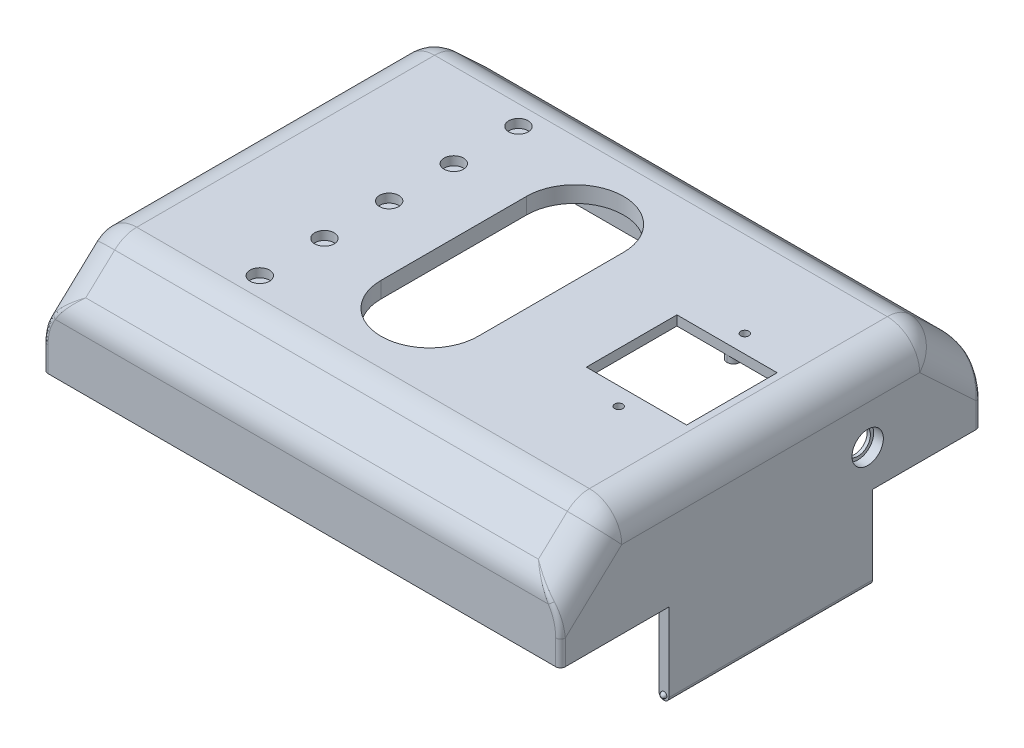
SolidWorks part; units mm, degrees
ref_plane "Front Plane" through (0, 0, 0) normal (0, 0, 1) x (1, 0, 0)
ref_plane "Top Plane" through (0, 0, 0) normal (0, 1, 0) x (1, 0, 0)
ref_plane "Right Plane" through (0, 0, 0) normal (1, 0, 0) x (0, 0, -1)
sketch "Sketch2" plane through (0, 0, 0) normal (0, 1, 0) x (1, 0, 0)
  line L0 (-80, 65) -> (80, -65) construction
  line L1 (-80, -65) -> (80, -65)
  line L2 (-80, -65) -> (-80, 65)
  line L3 (-80, 65) -> (80, 65)
  line L4 (80, -65) -> (80, 65)
  line L5 (-80, -65) -> (80, 65) construction
  point P4 (0, 0)
  dimension "D1" = 160
  dimension "D2" = 130
extrude "Boss-Extrude1" add sketch "Sketch2" along normal blind 5
sketch "Sketch3" plane through (-80, 0, 0) normal (-1, 0, 0) x (0, 0, 1)
  line L0 (-60, 4.8954) -> (60, 4.8954)
  line L1 (65, 5) -> (65, 0) construction
  line L2 (-65, 5) -> (65, 5) construction
  line L3 (-65, 5) -> (-65, 0) construction
  line L4 (65, 5) -> (65, 0)
  line L5 (-65, 5) -> (65, 5)
  line L6 (-65, 5) -> (-65, 0)
  arc A0 (-60, 4.8954) -> (-65, 0) centre (-60, -0.1057) ccw
  arc A1 (60, 4.8954) -> (65, 0) centre (60, -0.1057) cw
  point P2 (0, 4.8954)
  dimension "D1" = 120
  dimension "D2" = 5.0011
extrude "Cut-Extrude1" [suppressed] cut sketch "Sketch3" against normal through all
sketch "Sketch4" plane through (0, 0, 0) normal (0, -1, 0) x (1, 0, 0)
  line L0 (80, 65) -> (80, -65) construction
  line L1 (80, 31.5) -> (77, 31.5)
  line L2 (80, 31.5) -> (80, -31.5)
  line L3 (80, -31.5) -> (77, -31.5)
  line L4 (77, 31.5) -> (77, -31.5)
  point P6 (77, 0)
  dimension "D1" = 3
  dimension "D2" = 63
extrude "Boss-Extrude2" add sketch "Sketch4" along normal blind 25.75
sketch "Sketch15" plane through (-80, 0, 0) normal (-1, 0, 0) x (0, 0, 1)
  line L0 (-65, 0) -> (-65, 20)
  line L1 (-65, 20) -> (-50, 34)
  line L2 (-50, 34) -> (50, 34)
  line L3 (50, 34) -> (65, 20)
  line L4 (65, 20) -> (65, 0)
  line L5 (65, 0) -> (-65, 0)
  dimension "D1" = 34
  dimension "D2" = 20
  dimension "D3" = 100
extrude "Boss-Extrude5" add sketch "Sketch15" against normal blind 160
sketch "Sketch16" plane through (0, 0, 0) normal (0, -1, 0) x (1, 0, 0)
  line L1 (-76, 62) -> (76, 62)
  line L5 (-76, 62) -> (76, -62) construction
  line L6 (-76, -62) -> (76, 62) construction
  line L7 (-80, 65) -> (80, 65) construction
  line L8 (76, 62) -> (76, -62)
  line L9 (76, -62) -> (-63, -62)
  line L14 (-76, 62) -> (-76, -51.25)
  line L15 (-76, -51.25) -> (-62.8226, -51.25)
  line L16 (-62.8226, -51.25) -> (-63, -62)
  line L17 (-80, -65) -> (-80, 65) construction
  point P0 (0, 0)
  dimension "D1" = 139
  dimension "D2" = 3
  dimension "D3" = 113.25
  dimension "D4" = 4
extrude "Cut-Extrude9" cut sketch "Sketch16" against normal blind 20
sketch "Sketch17" plane through (0, 20, 0) normal (0, -1, 0) x (1, 0, 0)
  line L1 (-76, 50) -> (76, 50)
  line L2 (-76, 50) -> (-76, -50)
  line L3 (-76, -50) -> (76, -50)
  line L4 (76, 50) -> (76, -50)
  line L5 (-76, 50) -> (76, -50) construction
  line L6 (-76, -50) -> (76, 50) construction
  line L7 (80, -65) -> (-80, -65) construction
  line L8 (-80, -65) -> (-80, 65) construction
  point P0 (0, 0)
  dimension "D1" = 15
  dimension "D2" = 4
extrude "Cut-Extrude10" cut sketch "Sketch17" against normal offset from surface (9 mm away) 5 up to face at (0, 34, 0)
fillet "Fillet3" radius 10 10 edges at (-80, 27, 57.5) (-80, 34, 0) (-80, 27, -57.5) (80, 34, 0) (80, 27, 57.5) (0, 20, 65) (0, 34, 50) (80, 27, -57.5) (0, 34, -50) (0, 20, -65)
sketch "Sketch21" plane through (-80, 0, 0) normal (-1, 0, 0) x (0, 0, 1)
  line L0 (31.5, 0) -> (-31.5, 0) construction
  line L3 (-65, 6.3211) -> (-65, 0) construction
  circle A0 centre (-30, 12) radius 4.85
  dimension "D3" = 9.7
  dimension "D1" = 12
  dimension "D2" = 35
extrude "Cut-Extrude12" cut sketch "Sketch21" against normal through all
sketch "Sketch29" plane through (-13.2466, 34, -3.5381) normal (0, 1, 0) x (1, 0, 0)
  line L0 (10.2466, 18.9619) -> (10.2466, -26.0381) construction
  line L1 (25.2466, 18.9619) -> (25.2466, -26.0381)
  line L2 (-4.7534, 18.9619) -> (-4.7534, -26.0381)
  line L3 (90.5571, -68.5381) -> (-64.064, -68.5381) construction
  line L5 (-66.7534, -49.5965) -> (-66.7534, 42.5202) construction
  arc A0 (25.2466, 18.9619) -> (-4.7534, 18.9619) centre (10.2466, 18.9619) ccw
  arc A1 (-4.7534, -26.0381) -> (25.2466, -26.0381) centre (10.2466, -26.0381) ccw
  point P3 (10.2466, -3.5381)
  dimension "D2" = 15
  dimension "D1" = 45
  dimension "D3" = 65
  dimension "D4" = 77
extrude "Cut-Extrude13" cut sketch "Sketch29" against normal blind 10
sketch "Sketch30" plane through (0, 34, 0) normal (0, 1, 0) x (1, 0, 0)
  line L1 (77.3106, -65) -> (-77.3106, -65) construction
  line L2 (-77.3106, 65) -> (77.3106, 65) construction
  circle A0 centre (-38, -40) radius 3
  circle A5 centre (-38, -20) radius 3
  circle A6 centre (-38, 0) radius 3
  circle A7 centre (-38, 20) radius 3
  circle A8 centre (-38, 40) radius 3
  dimension "D1" = 25
  dimension "D2" = 6
  dimension "D3" = 38
  dimension "D5" = 25
  dimension "D4" = 5
extrude "Cut-Extrude14" cut sketch "Sketch30" against normal blind 2.7
sketch "Sketch32" plane through (0, 0, 0) normal (0, -1, 0) x (1, 0, 0)
  line L0 (80, -65) -> (-80, -65) construction
  line L1 (-80, -65) -> (-80, 65) construction
  circle A0 centre (-72, -59.25) radius 3
  dimension "D1" = 6
  dimension "D2" = 5.75
  dimension "D3" = 8
extrude "Cut-Extrude15" cut sketch "Sketch32" against normal blind 2.7
sketch "Sketch33" plane through (0, 29, 0) normal (0, 1, 0) x (1, 0, 0)
  line L0 (-77.3106, 65) -> (77.3106, 65) construction
  line L1 (37, 14) -> (68, 14)
  line L2 (37, 14) -> (37, -14)
  line L3 (37, -14) -> (68, -14)
  line L4 (68, 14) -> (68, -14)
  line L5 (37, 14) -> (68, -14) construction
  line L6 (37, -14) -> (68, 14) construction
  point P0 (52.5, 0)
  dimension "D1" = 31
  dimension "D2" = 28
  dimension "D3" = 52.5
  dimension "D4" = 65
extrude "Cut-Extrude16" cut sketch "Sketch33" along normal through all
sketch "Sketch37" plane through (0, 29, 0) normal (0, -1, 0) x (1, 0, 0)
  line L0 (37, 14) -> (68, 14) construction
  line L1 (33, 21.5) -> (69, 21.5)
  line L2 (33, 21.5) -> (33, -21.5)
  line L3 (33, -21.5) -> (69, -21.5)
  line L4 (69, 21.5) -> (69, -21.5)
  line L5 (33, 21.5) -> (69, -21.5) construction
  line L6 (33, -21.5) -> (69, 21.5) construction
  line L7 (50.5, 21.5) -> (54.5, 21.5)
  line L8 (50.5, 21.5) -> (50.5, 14)
  line L9 (50.5, 14) -> (54.5, 14)
  line L10 (54.5, 21.5) -> (54.5, 14)
  line L11 (68, -14) -> (37, -14) construction
  line L12 (50.5, -14) -> (54.5, -14)
  line L13 (50.5, -14) -> (50.5, -21.5)
  line L14 (50.5, -21.5) -> (54.5, -21.5)
  line L15 (54.5, -14) -> (54.5, -21.5)
  line L16 (-77.3106, -65) -> (77.3106, -65) construction
  line L19 (37, -14) -> (37, 14) construction
  line L21 (68, 14) -> (68, -14) construction
  circle A0 centre (52.5, 19.5) radius 1.25
  circle A1 centre (52.5, -19.5) radius 1.1265
  point P0 (51, 0)
  point P13 (52.5, 14)
  line M13 (68, 14) -> (68, -14)
  line M14 (68, -14) -> (37, -14)
  line M15 (37, -14) -> (37, 14)
  line M16 (37, 14) -> (68, 14)
  dimension "D6" = 2.5
  dimension "D8" = 2
  dimension "D11" = 5.5
  dimension "2.5" = 2.2529
  dimension "D12" = 2
  dimension "D10" = 16.5
  dimension "D2" = 4
  dimension "D3" = 1
  dimension "33" = 43
  dimension "D4" = 16.5
  dimension "D5" = 5.5
  dimension "D7" = 4
  dimension "D9" = 4
  dimension "D13" = 65
extrude "Cut-Extrude17" cut sketch "Sketch37" against normal blind 2 contours L13 L8 L1 L2 L3 M14 M15 M16 | L15 L3 L4 L1 L10 M14 M16 M13 region at (41.75, 29, 21.0358) region at (61.75, 29, 21.0462)
sketch "Sketch39" plane through (0, 29, 0) normal (0, -1, 0) x (1, 0, 0)
  line L0 (50.5, 14) -> (54.5, 14) construction
  line L1 (69, 21.5) -> (69, -21.5) construction
  line L2 (54.5, -14) -> (50.5, -14) construction
  line L3 (68, 14) -> (68, -14) construction
  circle A0 centre (52.5, 19.5) radius 1.25
  circle A1 centre (52.5, -19.5) radius 1.25
  dimension "D2" = 2.5
  dimension "D4" = 2.5
  dimension "D1" = 5.5
  dimension "D3" = 16.5
  dimension "D5" = 5.5
  dimension "D6" = 15.5
extrude "Cut-Extrude18" cut sketch "Sketch39" against normal through all
sketch "Sketch40" plane through (-76, 0, 0) normal (1, 0, 0) x (0, 0, -1)
  circle A0 centre (30, 12) radius 4.85
  circle A1 centre (30, 12) radius 4.85 construction
  dimension "D1" = 0
extrude "Boss-Extrude6" add sketch "Sketch40" against normal blind 1
sketch "Sketch43" plane through (76, 0, 0) normal (-1, 0, 0) x (0, 0, 1)
  circle A0 centre (-30, 12) radius 4.85
  dimension "D1" = 9.7
extrude "Boss-Extrude8" add sketch "Sketch43" against normal blind 1 separate body
sketch "Sketch44" plane through (76, 0, 0) normal (-1, 0, 0) x (0, 0, 1)
  circle A0 centre (-30, 12) radius 3.85
  circle A1 centre (-30, 12) radius 4.85 construction
  dimension "D1" = 1
extrude "Cut-Extrude22" cut sketch "Sketch44" against normal through all
sketch "Sketch45" plane through (-77, 0, 0) normal (-1, 0, 0) x (0, 0, 1)
  circle A0 centre (-30, 12) radius 3.85
  circle A1 centre (-30, 12) radius 4.85 construction
  dimension "D1" = 1
extrude "Cut-Extrude23" cut sketch "Sketch45" against normal through all
fillet "Fillet4" radius 8 1 edges at (-62.8226, 10, -51.25)
fillet "Fillet5" radius 5 5 edges at (-63, 10, -62) (-76, 10, -51.25) (76, 10, -62) (76, 10, 62) (-76, 10, 62)
fillet "Fillet7" radius 5 8 edges at (33, 30, -21.5) (54.5, 30, -21.5) (50.5, 30, -21.5) (69, 30, -21.5) (69, 30, 21.5) (54.5, 30, 21.5) (50.5, 30, 21.5) (33, 30, 21.5)
fillet "Fillet9" radius 2 4 edges at (50.5, 30, -14) (54.5, 30, -14) (54.5, 30, 14) (50.5, 30, 14)
fillet "Fillet11" radius 2 2 edges at (0, 20, 50) (0.8464, 20, -50)
sketch "Sketch47" plane through (0, 0, 31.5) normal (0, 0, 1) x (1, 0, 0)
  line L4 (78.5, -23.5267) -> (78.5, -25.15) construction
  line L5 (78.5, -23.35) -> (78.5, -25.15)
  line L6 (80, -25.75) -> (77, -25.75) construction
  line L7 (80, -25.75) -> (80, 0) construction
  arc A1 (78.5, -23.35) -> (78.5, -25.15) centre (78.5, -24.25) cw
  dimension "D3" = 1.5
  dimension "D1" = 0.9
  dimension "D2" = 1.5
revolve "Revolve11" add sketch "Sketch47" angle 360 about L4
ref_plane "Plane7" through (0, 0, 0) normal (0, 0, 1) x (1, 0, 0)
mirror "Mirror2" about plane through (0, 0, 0) normal (0, 0, 1) of "Revolve11"
fillet "Fillet12" radius 1.5 2 edges at (80, -25.75, 0) (77, -25.75, 0)
fillet "Fillet13" radius 1.5 12 edges at (73.9855, 19.64, -64.1715) (79.3034, 11.3372, -65) (73.9855, 19.64, 64.1715) (79.3034, 11.3372, 65) (-73.9855, 19.64, 64.1715) (-79.3034, 11.3372, 65) (-73.9855, 19.64, -64.1715) (-79.3034, 11.3372, -65) (80, 3.1606, -65) (80, 3.1606, 65) (-80, 3.1606, 65) (-80, 3.1606, -65)
